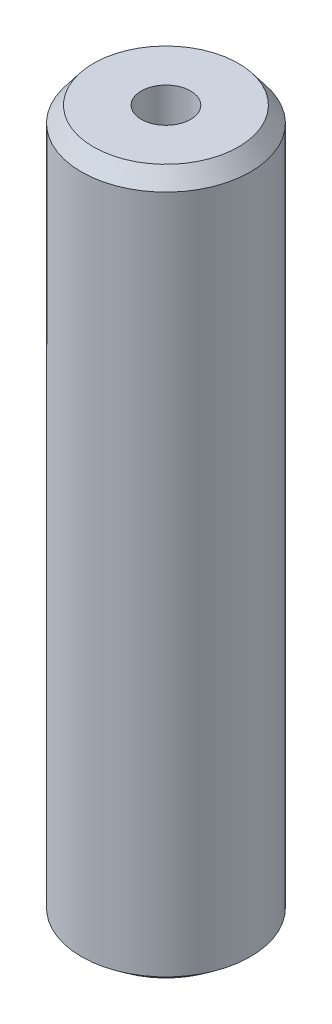
SolidWorks part; units mm, degrees
ref_plane "Front Plane" through (0, 0, 0) normal (0, 0, 1) x (1, 0, 0)
ref_plane "Top Plane" through (0, 0, 0) normal (0, 1, 0) x (1, 0, 0)
ref_plane "Right Plane" through (0, 0, 0) normal (1, 0, 0) x (0, 0, -1)
sketch "Sketch1" plane through (0, 0, 0) normal (0, 1, 0) x (1, 0, 0)
  circle A0 centre (0, 0) radius 25
  dimension "SHAFT_OD" = 50
extrude "Boss-Extrude1" add sketch "Sketch1" along normal blind 209.3082
sketch "Sketch2" plane through (0, 0, 0) normal (0, 1, 0) x (1, 0, 0)
  circle A0 centre (0, 0) radius 7.2996
  dimension "BORE_D" = 14.5991
extrude "Cut-Extrude1" cut sketch "Sketch2" along normal through all
chamfer "Chamfer1" distance 4.622 angle 37.551 2 edges at (0, 209.3082, 25) (0, 0, 25) first distance on face at (0, 209.3082, 25) first distance on face at (0, 0, 7.2996)
